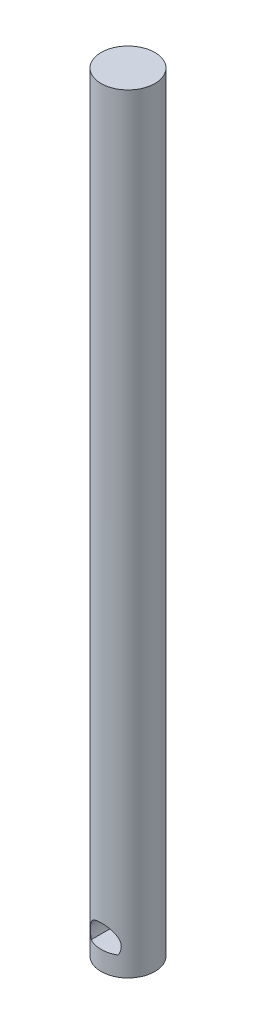
SolidWorks part; units mm, degrees
ref_plane "Front Plane" through (0, 0, 0) normal (0, 0, 1) x (1, 0, 0)
ref_plane "Top Plane" through (0, 0, 0) normal (0, 1, 0) x (1, 0, 0)
ref_plane "Right Plane" through (0, 0, 0) normal (1, 0, 0) x (0, 0, -1)
sketch "Sketch1" plane through (0, 0, 0) normal (0, 1, 0) x (1, 0, 0)
  circle A0 centre (0, 0) radius 3.5
extrude "Boss-Extrude1" add sketch "Sketch1" along normal blind 100
sketch "Sketch4" plane through (0, 0, 0) normal (0, 0, 1) x (1, 0, 0)
  line L2 (1.7323, 2.5005) -> (-1.7323, 2.5005)
  arc A0 (1.7323, 2.5005) -> (-1.7323, 2.5005) centre (0, 3.5) ccw
extrude "Cut-Extrude1" cut sketch "Sketch4" along normal blind 4.5 contours A0 L2
extrude "Cut-Extrude2" cut sketch "Sketch4<4>" against normal blind 2.5
sketch "Sketch4<4>" plane through (0, 0, 0) normal (0, 0, 1) x (1, 0, 0) same geometry as "Sketch4"
